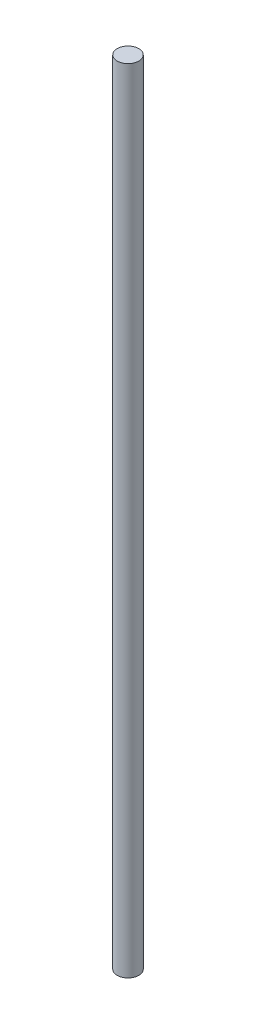
SolidWorks part; units mm, degrees
ref_plane "Front Plane" through (0, 0, 0) normal (0, 0, 1) x (1, 0, 0)
ref_plane "Top Plane" through (0, 0, 0) normal (0, 1, 0) x (1, 0, 0)
ref_plane "Right Plane" through (0, 0, 0) normal (1, 0, 0) x (0, 0, -1)
sketch "Sketch2" plane through (0, 0, 0) normal (0, 1, 0) x (1, 0, 0)
  circle A0 centre (0, 0) radius 6
  dimension "D1" = 12
extrude "Boss-Extrude1" add sketch "Sketch2" along normal blind 440
